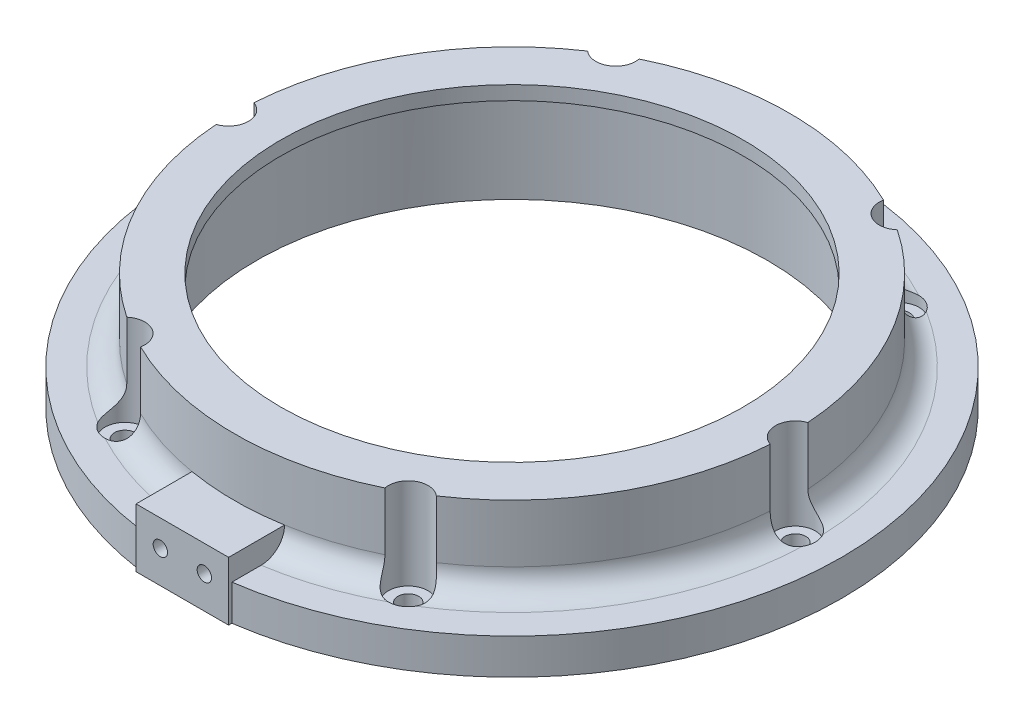
SolidWorks part; units mm, degrees
ref_plane "Front Plane" through (0, 0, 0) normal (0, 0, 1) x (1, 0, 0)
ref_plane "Top Plane" through (0, 0, 0) normal (0, 1, 0) x (1, 0, 0)
ref_plane "Right Plane" through (0, 0, 0) normal (1, 0, 0) x (0, 0, -1)
sketch "Sketch1" plane through (0, 0, 0) normal (0, 1, 0) x (1, 0, 0)
  circle A0 centre (0, 0) radius 61.25 construction
  circle A1 centre (0, 0) radius 55.25
  circle A2 centre (0, 0) radius 60
  dimension "D1" = 122.5
  dimension "D2" = 110.5
  dimension "D3" = 120
extrude "Boss-Extrude1" add sketch "Sketch1" along normal blind 22
sketch "Sketch2" plane through (0, 0, 0) normal (0, -1, 0) x (1, 0, 0)
  circle A0 centre (0, 0) radius 61.25 construction
  circle A1 centre (0, 0) radius 71.25
  circle A2 centre (0, 0) radius 60 construction
  circle A3 centre (0, 0) radius 60
  dimension "D1" = 122.5
  dimension "D2" = 10
extrude "Boss-Extrude2" add sketch "Sketch2" against normal blind 7.5
sketch "Sketch11" plane through (0, 22, 0) normal (0, 1, 0) x (1, 0, 0)
  circle A2 centre (0, 0) radius 60
  circle A3 centre (0, 0) radius 50
  dimension "D1" = 120
  dimension "D2" = 100
extrude "Boss-Extrude5" add sketch "Sketch11" along normal blind 3
hole_wizard "CBORE for M4 SBHCS1" positions "Sketch6" profile "Sketch5" counterbore size "M4" standard "ANSI Metric" end condition through all
sketch "Sketch6" plane through (0, 7.5, 0) normal (0, 1, 0) x (1, 0, 0)
  circle A0 centre (0, 0) radius 61.25 construction
  point P0 (-61.25, 0)
  dimension "D1" = 122.5
sketch "Sketch5" plane through (-61.25, 7.5, 0) normal (1, 0, 0) x (0, 0, 1)
  line L0 (0, 0) -> (0, 7.5)
  line L1 (0, 7.5) -> (2.25, 7.5)
  line L3 (2.25, 7.5) -> (2.25, 2.2)
  line L4 (2.25, 2.2) -> (4.3, 2.2)
  line L5 (4.3, 2.2) -> (4.3, 0)
  line L7 (4.3, 0) -> (0, 0)
  line L11 (0, -6.35) -> (0, 107.95) construction
  dimension "Thru Hole Dia." = 4.5
  dimension "Thru Hole Depth" = 7.5
  dimension "C'Bore Dia." = 8.6
  dimension "C'Bore Depth" = 2.2
fillet "Fillet2" radius 5 1 edges at (60, 7.5, 0)
sketch "Sketch7" plane through (0, 7.5, 0) normal (0, 1, 0) x (1, 0, 0)
  circle A1 centre (-61.25, 0) radius 4.3
  circle A2 centre (-61.25, 0) radius 4.3
  dimension "D1" = 0
extrude "Cut-Extrude1" cut sketch "Sketch7" along normal through all
pattern_circular "CirPattern1" count 6 over 360 about axis through (0, 7.5, 0) along (0, -1, 0) of "Cut-Extrude1", "CBORE for M4 SBHCS1"
sketch "Sketch10" plane through (0, 0, 0) normal (0, -1, 0) x (1, 0, 0)
  circle A0 centre (0, 0) radius 55.25 construction
  circle A1 centre (0, 0) radius 71.25
  circle A2 centre (0, 0) radius 71.25
  circle A3 centre (61.25, 0) radius 2.25 construction
  circle A4 centre (30.625, 53.0441) radius 2.25 construction
  circle A5 centre (-30.625, 53.0441) radius 2.25 construction
  circle A6 centre (-61.25, 0) radius 2.25 construction
  circle A7 centre (-30.625, -53.0441) radius 2.25 construction
  circle A8 centre (30.625, -53.0441) radius 2.25 construction
  circle A9 centre (0, 0) radius 55.25
  circle A10 centre (61.25, 0) radius 2.25
  circle A11 centre (30.625, 53.0441) radius 2.25
  circle A12 centre (-30.625, 53.0441) radius 2.25
  circle A13 centre (-61.25, 0) radius 2.25
  circle A14 centre (-30.625, -53.0441) radius 2.25
  circle A15 centre (30.625, -53.0441) radius 2.25
  dimension "D1" = 0
extrude "Boss-Extrude4" add sketch "Sketch10" along normal blind 0.2
ref_plane "Plane1" through (0, 0, 71.25) normal (0, 0, 1) x (1, 0, 0)
sketch "Sketch12" plane through (0, 0, 71.25) normal (0, 0, 1) x (1, 0, 0)
  line L0 (-71.25, -0.2) -> (71.25, -0.2) construction
  line L1 (10, -0.2) -> (-10, -0.2)
  line L2 (10, -0.2) -> (10, 12.5)
  line L3 (10, 12.5) -> (-10, 12.5)
  line L4 (-10, -0.2) -> (-10, 12.5)
  point P6 (0, 12.5)
  dimension "D1" = 20
  dimension "D2" = 12.7
extrude "Boss-Extrude6" add sketch "Sketch12" against normal up to surface (12.0892 mm away) up to face at (49.3101, 18.75, 28.4692)
sketch "Sketch13" plane through (0, 0, 71.25) normal (0, 0, 1) x (1, 0, 0)
  line L0 (0, 16.7615) -> (0, -14.5521) construction
  line L1 (-10, -0.2) -> (10, -0.2) construction
  circle A0 centre (4.75, 6.8) radius 1.55
  circle A1 centre (-4.75, 6.8) radius 1.55
  dimension "D1" = 4.75
  dimension "D2" = 3.1
  dimension "D3" = 7
extrude "Cut-Extrude2" cut sketch "Sketch13" against normal blind 8
